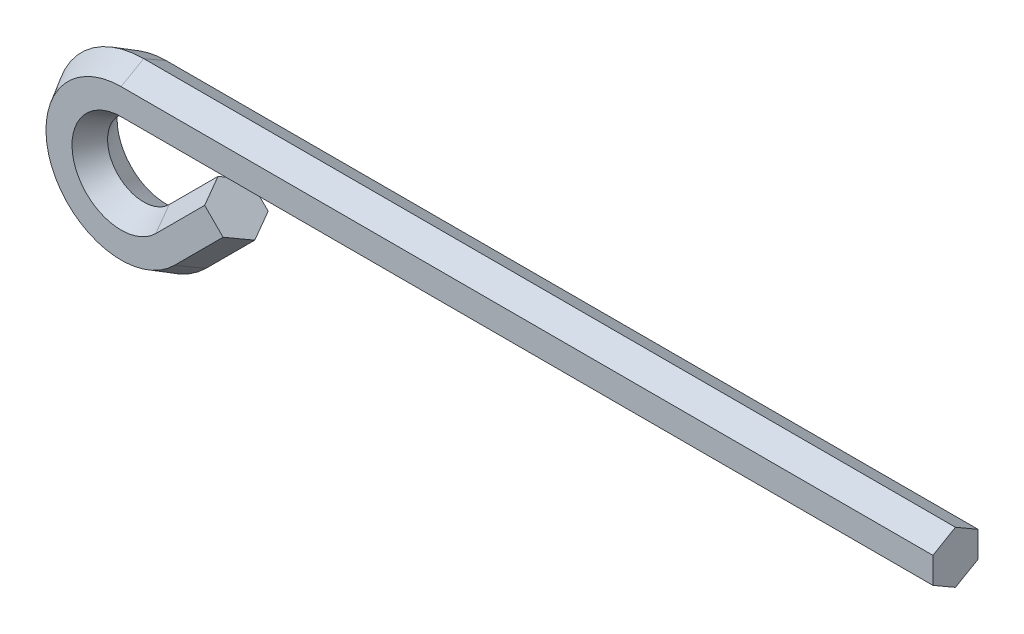
SolidWorks part; units mm, degrees
material "PW20:29:Sc:0:"
ref_plane "Front" through (0, 0, 0) normal (0, 0, 1) x (1, 0, 0)
ref_plane "Top" through (0, 0, 0) normal (0, 1, 0) x (1, 0, 0)
ref_plane "Right" through (0, 0, 0) normal (1, 0, 0) x (0, 0, -1)
other "DIMS"
sketch "Sketch1" plane through (0, 0, 0) normal (0, 0, 1) x (1, 0, 0)
  line L0 (90, 4) -> (0, 4)
  line L1 (2.8284, -2.8284) -> (8.2426, 2.5858)
  line L2 (8.2426, 2.5858) -> (9.6569, 4) construction
  arc A0 (0, 4) -> (2.8284, -2.8284) centre (0, 0) ccw
  dimension "Center_Rad" = 4
  dimension "Length" = 90
  dimension "Overlap" = 2
  dimension "Angle" = 45
ref_plane "Plane4" through (90, 4, 0) normal (-1, 0, 0) x (0, 0, 1)
sketch "Sketch2" plane through (90, 4, 0) normal (-1, 0, 0) x (0, 0, 1)
  line L0 (0, 0) -> (0, 5.7735) construction
  line L1 (-2.5, 4.3301) -> (0, 5.7735)
  line L2 (-2.5, 1.4434) -> (-2.5, 4.3301)
  line L3 (0, 0) -> (2.5, 1.4434)
  line L4 (2.5, 1.4434) -> (2.5, 4.3301)
  line L5 (2.5, 4.3301) -> (0, 5.7735)
  line L6 (0, 0) -> (-2.5, 1.4434)
  line L7 (2.5, 1.4434) -> (-2.5, 4.3301) construction
  line L8 (2.5, 4.3301) -> (-2.5, 1.4434) construction
  dimension "Hex_Diam" = 5
sweep "Base-Sweep" add profiles "Sketch2" path "Sketch1"
ref_axis "center_axis" [suppressed] through (0, 0, 52.5) along (0, 0, -1)
